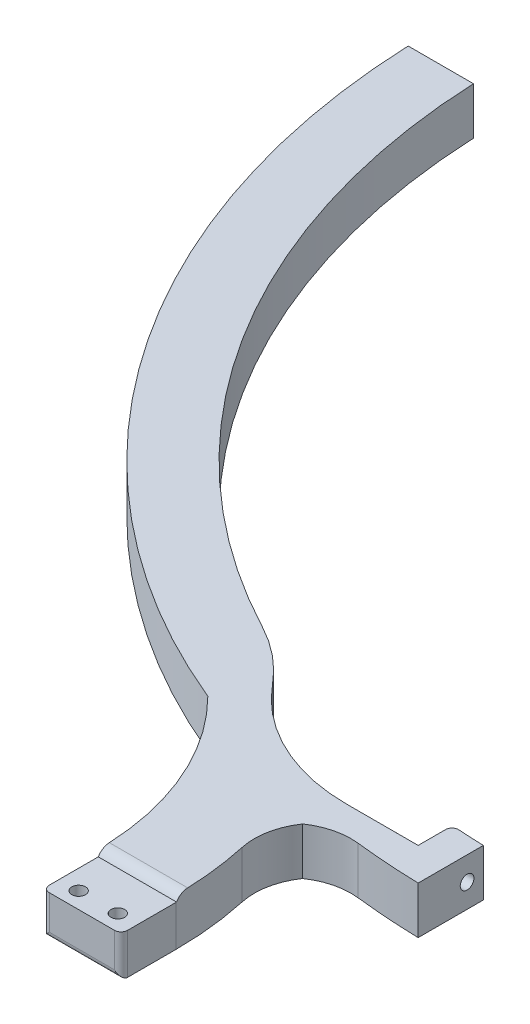
SolidWorks part; units mm, degrees
ref_plane "Front Plane" through (0, 0, 0) normal (0, 0, 1) x (1, 0, 0)
ref_plane "Top Plane" through (0, 0, 0) normal (0, 1, 0) x (1, 0, 0)
ref_plane "Right Plane" through (0, 0, 0) normal (1, 0, 0) x (0, 0, -1)
sketch "Sketch2" plane through (0, 0, 0) normal (0, 1, 0) x (1, 0, 0)
  line L2 (-17.6232, -113.6416) -> (-22.6232, -118.6416)
  line L3 (2, -135.0609) -> (-20, -135.0609) construction
  line L4 (-72.6986, -135.0609) -> (-43.9203, -106.2827) construction
  line L6 (-32, -135.0609) -> (-72.6986, -135.0609) construction
  line L8 (-32, -135.0609) -> (-32, -143.5109)
  line L9 (-32, -143.5109) -> (-20, -143.5109)
  line L10 (-20, -135.0609) -> (-20, -143.5109)
  line L12 (-26, -143.5109) -> (-3, -143.5109) construction
  line L13 (-3, -114.9609) -> (-3, -104.9571)
  line L14 (-3, -114.9609) -> (-3, -143.5109) construction
  line L24 (-114.9087, -4.5826) -> (-104.9, -4.5826)
  line L29 (-3, -114.9609) -> (-3, -104.9571)
  arc A1 (-104.9, -4.5826) -> (-3, -104.9571) centre (0, 0) ccw
  arc A3 (-114.9087, -4.5826) -> (-43.9203, -106.2827) centre (0, 0) ccw
  arc A4 (-20, -135.0609) -> (-22.6232, -118.6416) centre (-72.6986, -135.0609) ccw
  arc A5 (-32, -135.0609) -> (-43.9203, -106.2827) centre (-72.6986, -135.0609) ccw
  arc A6 (-17.6232, -113.6416) -> (-3, -114.9609) centre (0, 0) ccw
  dimension "D1" = 210
  dimension "D2" = 10
  dimension "D10" = 5
  dimension "D12" = 52.6986
  dimension "D3" = 3
  dimension "D4" = 45
  dimension "D5" = 12
  dimension "D6" = 23
  dimension "D7" = 8.45
  dimension "D8" = 20.1
  dimension "D9" = 5
  dimension "D11" = 10.0087
extrude "Boss-Extrude1" add sketch "Sketch2" along normal blind 7.25 contours A4 A6 L13 A1 L24 A3 A5 L8 L9 L10 region at (-21.3846, 0, 114.8802)
sketch "Sketch4" plane through (0, 0, 4.5826) normal (0, 0, -1) x (-1, 0, 0)
  line L0 (114.9087, 0) -> (104.9, 7.25) construction
  line L2 (111.557, 5.2791) -> (109.2981, 5.8833)
  line L3 (109.2981, 5.8833) -> (107.6454, 4.2292)
  line L4 (107.6454, 4.2292) -> (108.2516, 1.9709)
  line L5 (108.2516, 1.9709) -> (110.5105, 1.3667)
  line L6 (110.5105, 1.3667) -> (112.1632, 3.0208)
  line L7 (112.1632, 3.0208) -> (111.557, 5.2791)
  circle A0 centre (109.9043, 3.625) radius 2.025 construction
  dimension "D1" = 4.05
extrude "Cut-Extrude2" cut sketch "Sketch4" against normal blind 2
sketch "Sketch5" plane through (0, 0, 4.5826) normal (0, 0, -1) x (-1, 0, 0)
  line L0 (104.9, 3.625) -> (114.9087, 3.625) construction
  line L1 (104.9, 7.25) -> (104.9, 0) construction
  line L2 (114.9087, 7.25) -> (114.9087, 0) construction
  circle A0 centre (109.9043, 3.625) radius 2.3383
sketch "Sketch6" plane through (0, 7.25, 0) normal (0, 1, 0) x (1, 0, 0)
  line L0 (-29, -141.0109) -> (-23, -141.0109) construction
  line L3 (-23, -141.0109) -> (-20, -141.0109) construction
  line L4 (-20, -135.0609) -> (-20, -143.5109) construction
  line L5 (-29, -141.0109) -> (-32, -141.0109) construction
  line L6 (-32, -135.0609) -> (-32, -143.5109) construction
  circle A0 centre (-29, -141.0109) radius 1.05
  circle A1 centre (-23, -141.0109) radius 1.05
  dimension "D1" = 2.1
  dimension "D2" = 2.5
  dimension "D3" = 6
extrude "Cut-Extrude3" cut sketch "Sketch6" against normal through all
fillet "Fillet1" radius 1 4 edges at (-20, 3.625, 143.5109) (-32, 3.625, 143.5109) (-26, 0, 143.5109) (-26, 7.25, 143.5109)
sketch "Sketch13" plane through (0, 7.25, 0) normal (0, 1, 0) x (1, 0, 0)
  line L2 (-3, -114.9609) -> (-3, -104.9571) construction
  line L7 (-8, -109.959) -> (-19, -109.959)
  line L15 (-8, -92.8655) -> (-8, -109.959)
  line L19 (-49, -92.8655) -> (-8, -92.8655)
  arc A1 (-104.9, -4.5826) -> (-3, -104.9571) centre (0, 0) ccw construction
  arc A2 (-40.4914, -99.8047) -> (-49, -92.8655) centre (-61.9828, -117.4706) ccw
  arc A4 (-40.4914, -99.8047) -> (-19, -109.959) centre (-19, -82.1388) ccw
  point P8 (-3, -109.959)
  dimension "D1" = 11
  dimension "D2" = 5
  dimension "D3" = 30
extrude "Cut-Extrude6" cut sketch "Sketch13" against normal blind 10
sketch "Sketch14" plane through (-3, 0, 0) normal (1, 0, 0) x (0, 0, -1)
  line L0 (-109.959, 7.25) -> (-104.9571, 7.25) construction
  line L1 (-114.9609, 7.25) -> (-104.9571, 7.25) construction
  line L2 (-107.4581, 7.25) -> (-107.4581, 0) construction
  line L3 (-114.9609, 0) -> (-104.9571, 0) construction
  circle A0 centre (-107.4581, 3.625) radius 1.05
  dimension "D1" = 2.1
extrude "Cut-Extrude7" cut sketch "Sketch14" against normal up to surface (5 mm away) up to face at (-8, 3.625, 107.3269)
fillet "Fillet3" radius 1 1 edges at (-8, 3.625, 104.6948)
fillet "Fillet4" radius 10 2 edges at (-22.6232, 3.625, 118.6416) (-17.6232, 3.625, 113.6416)
sketch "Sketch16" plane through (0, 7.25, 0) normal (0, 1, 0) x (1, 0, 0)
  line L1 (-5.3571, -135) -> (-45.3571, -135)
  line L2 (-5.3571, -135) -> (-5.3571, -150)
  line L3 (-5.3571, -150) -> (-45.3571, -150)
  line L4 (-45.3571, -135) -> (-45.3571, -150)
  dimension "D1" = 135
  dimension "D2" = 40
  dimension "D3" = 15
extrude "Cut-Extrude8" cut sketch "Sketch16" against normal blind 1
fillet "Fillet5" radius 2 1 edges at (-26, 7.25, 135)
